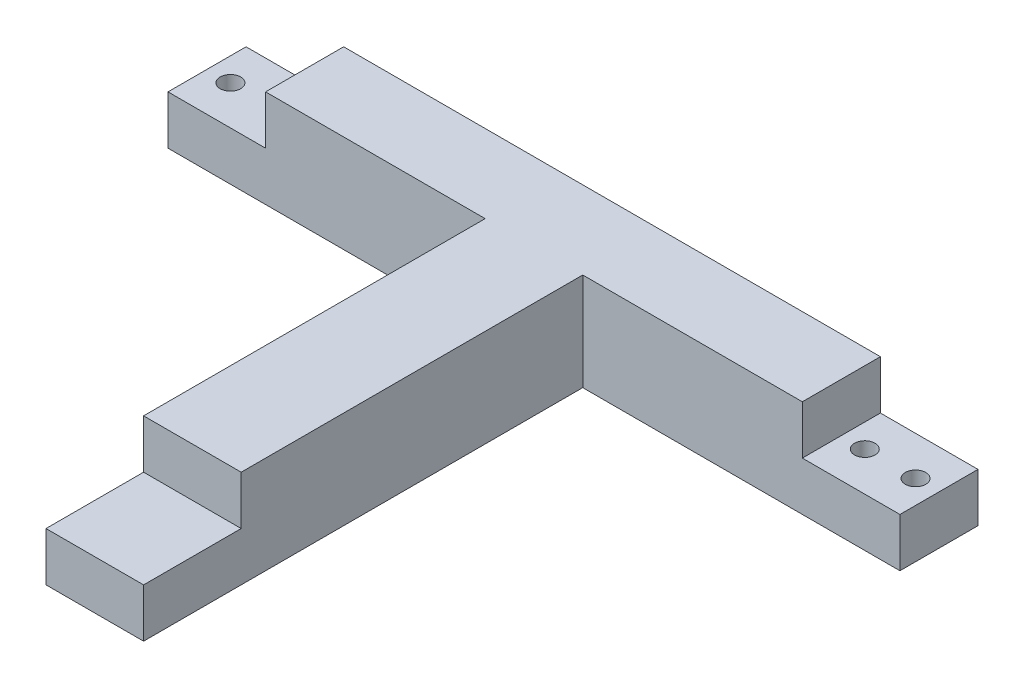
SolidWorks part; units mm, degrees
ref_plane "前视基准面" through (0, 0, 0) normal (0, 0, 1) x (1, 0, 0)
ref_plane "上视基准面" through (0, 0, 0) normal (0, 1, 0) x (1, 0, 0)
ref_plane "右视基准面" through (0, 0, 0) normal (1, 0, 0) x (0, 0, -1)
other "Configuration Table"
sketch "草图1" plane through (0, 0, 0) normal (0, 1, 0) x (1, 0, 0)
  line L1 (75, -8) -> (-75, -8)
  line L2 (75, -8) -> (75, 8)
  line L3 (75, 8) -> (-75, 8)
  line L4 (-75, -8) -> (-75, 8)
  line L5 (75, -8) -> (-75, 8) construction
  line L6 (75, 8) -> (-75, -8) construction
  point P0 (0, 0)
  dimension "D1" = 150
  dimension "D2" = 16
extrude "凸台-拉伸1" add sketch "草图1" along normal blind 10 contours L3 L4 L1 L2
sketch "草图2" plane through (0, 10, 0) normal (0, 1, 0) x (1, 0, 0)
  line L0 (75, 8) -> (-75, 8) construction
  line L1 (-55, 8) -> (55, 8)
  line L2 (-55, 8) -> (-55, -8)
  line L3 (-55, -8) -> (55, -8)
  line L4 (55, 8) -> (55, -8)
  line L5 (75, -8) -> (-75, -8) construction
  line L6 (-75, -8) -> (-75, 8) construction
  line L7 (75, -8) -> (75, 8) construction
  circle A0 centre (-70.2, 0) radius 2.1
  circle A1 centre (-59.8, 0) radius 2.1
  point P16 (0, 0)
  line M5 (75, 8) -> (-75, 8)
  line M7 (-75, -8) -> (75, -8)
  dimension "D5" = 4.2
  dimension "D8" = 4.2
  dimension "D1" = 20
  dimension "D2" = 20
  dimension "D3" = 110
  dimension "D4" = 8
  dimension "D6" = 4.8
  dimension "D7" = 4.8
extrude "凸台-拉伸2" add sketch "草图2" along normal blind 10 contours L4 L2 M5 M7 region at (0, 10, 0)
sketch "草图4" plane through (0, 10, 0) normal (0, 1, 0) x (1, 0, 0)
  line L0 (-75, -8) -> (-75, 8) construction
  line L1 (-55, 8) -> (-55, -8) construction
  line L2 (-55, -8) -> (-75, -8) construction
  circle A0 centre (-70.2, 0) radius 2.1
  circle A1 centre (-59.8, 0) radius 2.1
  point P10 (0, 0)
  dimension "D3" = 4.2
  dimension "D4" = 4.2
  dimension "D1" = 4.8
  dimension "D2" = 4.8
  dimension "D5" = 8
extrude "切除-拉伸1" cut sketch "草图4" against normal blind 10
sketch "草图5" plane through (0, 10, 0) normal (0, 1, 0) x (1, 0, 0)
  line L0 (75, -8) -> (75, 8) construction
  line L1 (55, 8) -> (55, -8) construction
  line L2 (75, -8) -> (55, -8) construction
  circle A0 centre (59.8, 0) radius 2.1
  circle A1 centre (70.2, 0) radius 2.1
  point P10 (0, 0)
  point P11 (0, 0)
  dimension "D3" = 4.2
  dimension "D4" = 4.2
  dimension "D1" = 4.8
  dimension "D2" = 4.8
  dimension "D5" = 8
extrude "切除-拉伸2" cut sketch "草图5" against normal blind 10
sketch "草图6" plane through (0, 0, 8) normal (0, 0, 1) x (1, 0, 0)
  line L0 (-55, 20) -> (55, 0) construction
  line L1 (75, 0) -> (-75, 0) construction
  line L2 (55, 20) -> (-55, 0) construction
  line L3 (-55, 20) -> (55, 20) construction
  line L4 (10, 0) -> (-10, 0)
  line L5 (10, 0) -> (10, 20)
  line L6 (10, 20) -> (-10, 20)
  line L7 (-10, 0) -> (-10, 20)
  line L8 (10, 0) -> (-10, 20) construction
  line L9 (10, 20) -> (-10, 0) construction
  point P5 (0, 10)
  dimension "D1" = 20
extrude "凸台-拉伸3" add sketch "草图6" along normal blind 70
sketch "草图7" plane through (0, 0, 78) normal (0, 0, 1) x (1, 0, 0)
  line L0 (-10, 10) -> (10, 10)
  line L1 (-10, 20) -> (-10, 0) construction
  line L2 (10, 0) -> (10, 20) construction
  line L3 (10, 10) -> (10, 0)
  line L4 (10, 0) -> (-10, 0)
  line L5 (-10, 0) -> (-10, 10)
extrude "凸台-拉伸4" add sketch "草图7" along normal blind 20
sketch "草图8" plane through (0, 10, 0) normal (0, 1, 0) x (1, 0, 0)
  line L0 (10, -98) -> (-10, -98) construction
  line L1 (10, -78) -> (-10, -78) construction
  line L2 (10, -98) -> (10, -78) construction
  circle A0 centre (0, -82.8) radius 2.1
  circle A1 centre (0, -93.2) radius 2.1
  point P10 (0, 0)
  dimension "D3" = 4.2
  dimension "D4" = 4.2
  dimension "D1" = 4.8
  dimension "D2" = 4.8
  dimension "D5" = 10
